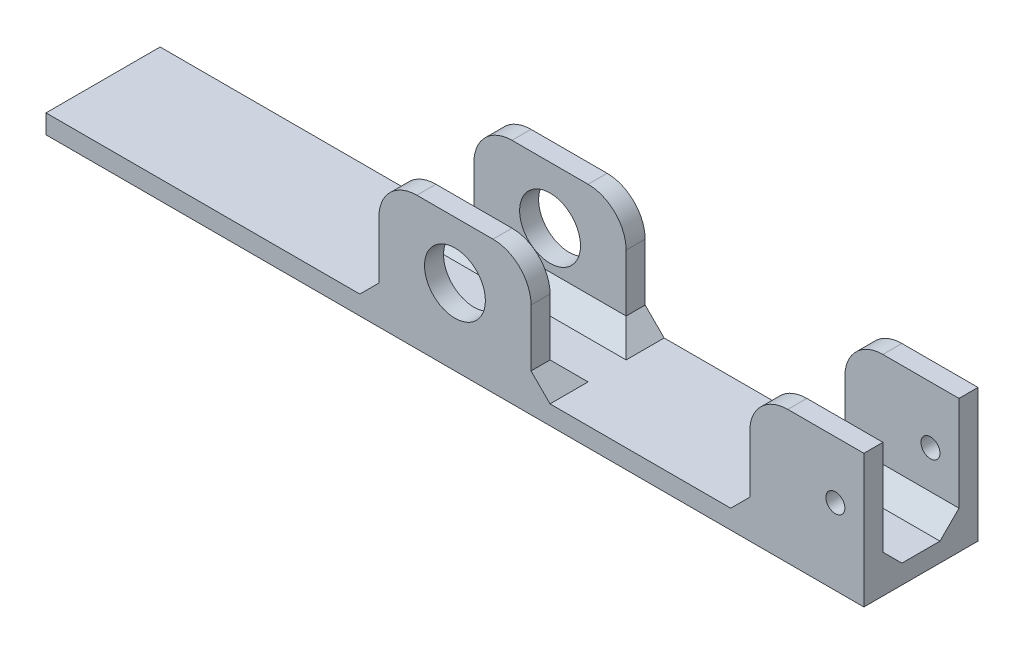
SolidWorks part; units mm, degrees
ref_plane "Front Plane" through (0, 0, 0) normal (0, 0, 1) x (1, 0, 0)
ref_plane "Top Plane" through (0, 0, 0) normal (0, 1, 0) x (1, 0, 0)
ref_plane "Right Plane" through (0, 0, 0) normal (1, 0, 0) x (0, 0, -1)
sketch "Sketch2" plane through (0, 0, 0) normal (0, 1, 0) x (1, 0, 0)
  line L1 (107.5, 15) -> (-107.5, 15)
  line L2 (107.5, 15) -> (107.5, -15)
  line L3 (107.5, -15) -> (-107.5, -15)
  line L4 (-107.5, 15) -> (-107.5, -15)
  line L5 (107.5, 15) -> (-107.5, -15) construction
  line L6 (107.5, -15) -> (-107.5, 15) construction
  point P0 (0, 0)
  dimension "D1" = 215
  dimension "D2" = 30
extrude "Boss-Extrude1" add sketch "Sketch2" along normal blind 5
sketch "HOLES TBD" plane through (0, 5, 0) normal (0, 1, 0) x (1, 0, 0)
  line L0 (100, 0) -> (-100, 0) construction
  circle A0 centre (-100, 0) radius 2.8385
  circle A1 centre (100, 0) radius 2.8385
  point P4 (0, 0)
  point P7 (0, 0)
  dimension "D2" = 5.6769
  dimension "D1" = 200
sketch "Sketch4" plane through (0, 5, 0) normal (0, 1, 0) x (1, 0, 0)
  line L0 (-107.5, -15) -> (107.5, -15) construction
  line L1 (107.5, -15) -> (77.5, -15)
  line L2 (107.5, -15) -> (107.5, -10)
  line L3 (107.5, -10) -> (77.5, -10)
  line L4 (77.5, -15) -> (77.5, -10)
  line L5 (107.5, -15) -> (77.5, -10) construction
  line L6 (107.5, -10) -> (77.5, -15) construction
  line L7 (-20, -15) -> (20, -15)
  line L8 (-20, -15) -> (-20, -10)
  line L9 (-20, -10) -> (20, -10)
  line L10 (20, -15) -> (20, -10)
  line L11 (-20, -15) -> (20, -10) construction
  line L12 (-20, -10) -> (20, -15) construction
  line L13 (0, 0) -> (0, -15) construction
  line L14 (-100, 0) -> (100, 0) construction
  line L15 (-20, 10) -> (20, 15) construction
  line L16 (-20, 15) -> (20, 10) construction
  line L17 (107.5, 10) -> (77.5, 15) construction
  line L18 (107.5, 15) -> (77.5, 10) construction
  line L19 (20, 15) -> (20, 10)
  line L20 (-20, 10) -> (20, 10)
  line L21 (-20, 15) -> (-20, 10)
  line L22 (-20, 15) -> (20, 15)
  line L23 (77.5, 15) -> (77.5, 10)
  line L24 (107.5, 10) -> (77.5, 10)
  line L25 (107.5, 15) -> (107.5, 10)
  line L26 (107.5, 15) -> (77.5, 15)
  point P4 (92.5, -12.5)
  point P10 (0, -12.5)
  point P28 (0, 12.5)
  point P29 (92.5, 12.5)
  dimension "D1" = 5
  dimension "D2" = 30
  dimension "D3" = 40
extrude "Boss-Extrude2" add sketch "Sketch4" along normal blind 30
sketch "Sketch5" plane through (0, 0, 15) normal (0, 0, 1) x (1, 0, 0)
  line L0 (0, 5) -> (0, 20) construction
  line L1 (100, 5) -> (100, 20) construction
  line L2 (102.8385, 5) -> (97.1616, 5) construction
  line L3 (-20, 20) -> (107.5, 20) construction
  line L4 (-20, 35) -> (-20, 5) construction
  line L5 (107.5, 35) -> (107.5, 0) construction
  circle A0 centre (0, 20) radius 8
  circle A1 centre (100, 20) radius 2.5
  dimension "D1" = 16
  dimension "D2" = 5
extrude "Bearing holes" cut sketch "Sketch5" against normal through all
chamfer "Chamfer1" distance 5 angle 45 10 edges at (92.5, 5, -10) (0, 5, -10) (0, 5, 10) (92.5, 5, 10) (77.5, 5, -12.5) (-20, 5, -12.5) (20, 5, -12.5) (-20, 5, 12.5) (20, 5, 12.5) (77.5, 5, 12.5)
fillet "Fillet1" radius 10 6 edges at (-20, 35, 12.5) (-20, 35, -12.5) (20, 35, -12.5) (20, 35, 12.5) (77.5, 35, 12.5) (77.5, 35, -12.5)
